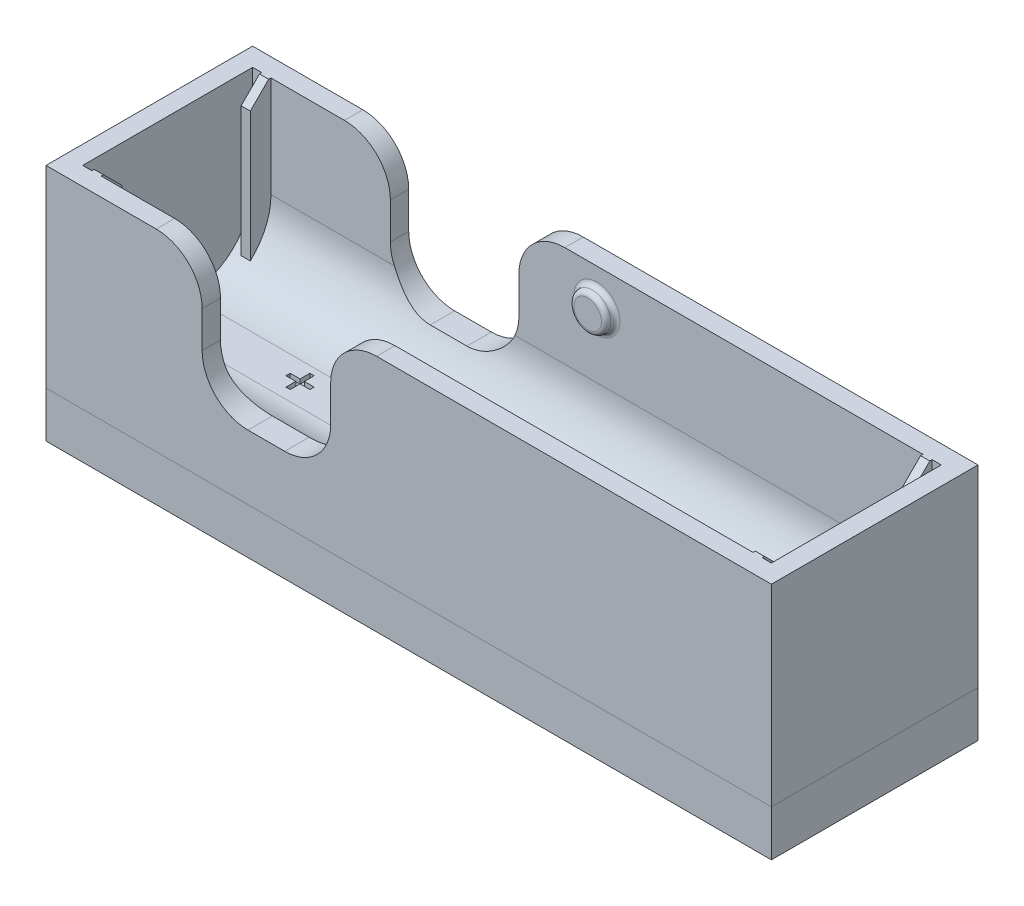
SolidWorks part; units mm, degrees
ref_plane "Спереди" through (0, 0, 0) normal (0, 0, 1) x (1, 0, 0)
ref_plane "Сверху" through (0, 0, 0) normal (0, 1, 0) x (1, 0, 0)
ref_plane "Справа" through (0, 0, 0) normal (1, 0, 0) x (0, 0, -1)
other "Configuration Table"
sketch "Эскиз1" plane through (0, 0, 0) normal (0, 1, 0) x (1, 0, 0)
  line L0 (0, 0) -> (97.2692, 0) construction
  line L1 (36.5, 9.25) -> (36.5, 7)
  line L2 (-37.5, -9.25) -> (37.5, -9.25)
  line L3 (-37.5, -9.25) -> (-37.5, 9.25)
  line L4 (-37.5, 9.25) -> (37.5, 9.25)
  line L5 (37.5, -9.25) -> (37.5, 9.25)
  line L6 (-37.5, -9.25) -> (37.5, 9.25) construction
  line L7 (-37.5, 9.25) -> (37.5, -9.25) construction
  line L8 (35.5, 9.25) -> (35.5, 7)
  line L9 (-36.5, 9.25) -> (-36.5, 7)
  line L10 (-35.5, 9.25) -> (-35.5, 7)
  line L11 (-36.5, 7) -> (-35.5, 7)
  line L12 (-36.5, -7) -> (-35.5, -7)
  line L13 (-35.5, -7) -> (-35.5, -9.25)
  line L14 (-36.5, -7) -> (-36.5, -9.25)
  line L15 (35.5, 7) -> (36.5, 7)
  line L16 (35.5, -7) -> (36.5, -7)
  line L17 (35.5, -7) -> (35.5, -9.25)
  line L18 (36.5, -7) -> (36.5, -9.25)
  line L19 (-36.5, 2.5) -> (-36.5, -2.5)
  line L20 (36.5, 2.5) -> (36.5, -2.5)
  line L21 (-37.5, 2.5) -> (-36.5, 2.5)
  line L22 (-37.5, -2.5) -> (-36.5, -2.5)
  line L23 (36.5, 2.5) -> (37.5, 2.5)
  line L24 (36.5, -2.5) -> (37.5, -2.5)
  line L25 (-39.5, 11.25) -> (39.5, 11.25)
  line L26 (39.5, -11.25) -> (39.5, 11.25)
  line L27 (-39.5, -11.25) -> (39.5, -11.25)
  line L28 (-39.5, -11.25) -> (-39.5, 11.25)
  point P1 (0, 0)
  point P34 (0, 0)
  point P39 (0, 0)
  point P40 (0, 0)
  point P41 (0, 0)
  point P42 (0, 0)
  point P43 (0, 0)
  point P44 (0, 0)
  dimension "D1" = 18.5
  dimension "D2" = 75
  dimension "D3" = 1
  dimension "D4" = 1
  dimension "D5" = 1
  dimension "D6" = 1
  dimension "D7" = 7
  dimension "D8" = 2.5
  dimension "D9" = 2.5
  dimension "D10" = 1
  dimension "D11" = 1
  dimension "D12" = 2
extrude "Бобышка-Вытянуть1" add sketch "Эскиз1" along normal blind 18 contours L28 L27 L26 L25 L5 L2 L3 L4 | L9 L11 L10 L4 | L12 L14 L2 L13 | L8 L15 L1 L4 | L18 L16 L17 L2 region at (36, 0, -8.125) region at (-36, 0, -8.125) region at (36, 0, 8.125) region at (-36, 0, 8.125) region at (0, 0, -10.4286)
extrude "Бобышка-Вытянуть2" add sketch "Эскиз1<4>" against normal blind 3 contours L28 L27 L26 L25 L5 L2 L3 L4 | L24 L20 L23 L5 L4 L1 L15 L8 L10 L11 L9 L3 L21 L19 L22 L2 L14 L12 L13 L17 L16 L18 | L12 L14 L2 L13 | L9 L11 L10 L4 | L18 L16 L17 L2 | L8 L15 L1 L4 region at (0, 0, 0) region at (36, 0, -8.125) region at (-36, 0, -8.125) region at (36, 0, 8.125) region at (-36, 0, 8.125) region at (0, 0, -10.4286)
sketch "Эскиз1<4>" plane through (0, 0, 0) normal (0, 1, 0) x (1, 0, 0) same geometry as "Эскиз1"
fillet "Скругление1" radius 7 2 edges at (0, 0, 9.25) (0, 0, -9.25)
sketch "Эскиз2" plane through (0, 0, 0) normal (0, 1, 0) x (1, 0, 0)
  text T0 "+"
  text T1 "<b>-</b>"
  point P2 (16.1974, -0.414)
  point P3 (17.3083, -1.7604)
  point P4 (19.9622, -1.093)
  point P5 (18.7279, -1.7604)
  point P6 (21.0115, -1.2781)
extrude "Вырез-Вытянуть1" cut sketch "Эскиз2" against normal blind 0.5
sketch "Эскиз3" plane through (0, 0, 11.25) normal (0, 0, 1) x (1, 0, 0)
  line L0 (-39.5, 18) -> (39.5, 18) construction
  line L1 (-21.5, 18) -> (-8.5, 18)
  line L2 (-22.4975, 13) -> (-22.4975, 9.0356)
  line L3 (-17.4975, 4.0356) -> (-13.4975, 4.0356)
  line L4 (-8.4975, 13) -> (-8.4975, 9.0356)
  line L5 (-27.5, 18) -> (-21.5, 18)
  line L6 (-8.5, 18) -> (-3.4975, 18)
  arc A0 (-13.4975, 4.0356) -> (-8.4975, 9.0356) centre (-13.4975, 9.0356) ccw
  arc A1 (-22.4975, 9.0356) -> (-17.4975, 4.0356) centre (-17.4975, 9.0356) ccw
  arc A2 (-3.4975, 18) -> (-8.4975, 13) centre (-3.4975, 13) ccw
  arc A3 (-27.5, 18) -> (-22.4975, 13) centre (-27.4975, 13) cw
  point P9 (-8.4975, 4.0356)
  point P12 (-22.4975, 4.0356)
  dimension "D4" = 5
  dimension "D5" = 5
  dimension "D1" = 14
  dimension "D2" = 14
  dimension "D3" = 18
extrude "Вырез-Вытянуть2" cut sketch "Эскиз3" against normal blind 30.5
chamfer "Фаска1" distance 2 angle 45 4 edges at (36, 18, 7) (36, 18, -7) (-36, 18, 7) (-36, 18, -7)
sketch "Эскиз4" plane through (0, 0, 9.25) normal (0, 0, -1) x (-1, 0, 0)
  line L0 (0, 0) -> (0, 28.1341) construction
  circle A0 centre (0, 14) radius 2
  point P4 (0, 14)
  dimension "D1" = 4
  dimension "D2" = 14
extrude "Бобышка-Вытянуть4" add sketch "Эскиз4" along normal blind 1
sketch "Эскиз5" plane through (0, 0, -9.25) normal (0, 0, 1) x (1, 0, 0)
  line L0 (0, 0) -> (0, 24.5494) construction
  circle A0 centre (0, 14) radius 2
  dimension "D1" = 4
  dimension "D2" = 14
extrude "Бобышка-Вытянуть5" add sketch "Эскиз5" along normal blind 1
fillet "Скругление3" radius 0.5 4 edges at (-2, 14, 8.25) (-2, 14, 9.25) (2, 14, -8.25) (-2, 14, -9.25)
sketch "Эскиз6" plane through (0, -3, 0) normal (0, -1, 0) x (1, 0, 0)
  line L0 (-37.5, 6.25) -> (-37.5, -6.25)
  line L1 (-39.5, 11.25) -> (39.5, 11.25)
  line L2 (-39.5, 11.25) -> (-39.5, -11.25)
  line L3 (-39.5, -11.25) -> (39.5, -11.25)
  line L4 (39.5, 11.25) -> (39.5, -11.25)
  line L5 (-34.5, -9.25) -> (34.5, -9.25)
  line L6 (37.5, 6.25) -> (37.5, -6.25)
  line L7 (-34.5, 9.25) -> (34.5, 9.25)
  line L8 (-39.5, 6.25) -> (-34.5, 11.25) construction
  line L9 (-39.5, 11.25) -> (-34.5, 11.25)
  line L10 (-39.5, 11.25) -> (-39.5, 6.25)
  line L11 (-39.5, 6.25) -> (-36.5, 6.25)
  line L12 (-34.5, 11.25) -> (-34.5, 8.25)
  line L13 (-39.5, -11.25) -> (-34.5, -11.25)
  line L14 (-39.5, -11.25) -> (-39.5, -6.25)
  line L15 (-39.5, -6.25) -> (-36.5, -6.25)
  line L16 (-34.5, -11.25) -> (-34.5, -8.25)
  line L17 (39.5, -11.25) -> (34.5, -11.25)
  line L18 (39.5, -11.25) -> (39.5, -6.25)
  line L19 (39.5, -6.25) -> (36.5, -6.25)
  line L20 (34.5, -11.25) -> (34.5, -8.25)
  line L21 (39.5, 11.25) -> (34.5, 11.25)
  line L22 (39.5, 11.25) -> (39.5, 6.25)
  line L23 (39.5, 6.25) -> (36.5, 6.25)
  line L24 (34.5, 11.25) -> (34.5, 8.25)
  line L25 (-37.5, 9.25) -> (37.5, 9.25) construction
  line L26 (-37.5, 9.25) -> (-37.5, -9.25) construction
  line L27 (-37.5, -9.25) -> (37.5, -9.25) construction
  line L28 (37.5, 9.25) -> (37.5, -9.25) construction
  line L29 (-39.5, -6.25) -> (-34.5, -11.25) construction
  line L30 (34.5, 11.25) -> (39.5, 6.25) construction
  line L31 (34.5, -11.25) -> (39.5, -6.25) construction
  arc A0 (36.5, -6.25) -> (34.5, -8.25) centre (36.5, -8.25) ccw
  arc A1 (34.5, 8.25) -> (36.5, 6.25) centre (36.5, 8.25) ccw
  arc A2 (-34.5, -8.25) -> (-36.5, -6.25) centre (-36.5, -8.25) ccw
  arc A3 (-34.5, 8.25) -> (-36.5, 6.25) centre (-36.5, 8.25) cw
  circle A4 centre (-37, 8.75) radius 0.5
  circle A5 centre (37, 8.75) radius 0.5
  circle A6 centre (37, -8.75) radius 0.5
  circle A7 centre (-37, -8.75) radius 0.5
  point P38 (-34.5, 6.25)
  point P39 (-37, 8.75)
  point P40 (-37, -8.75)
  point P41 (37, -8.75)
  point P42 (37, 8.75)
  line M9 (37.5, 2.5) -> (37.5, -2.5)
  line M16 (-37.5, -2.5) -> (-37.5, 2.5)
  line M17 (-39.5, 11.25) -> (-39.5, -11.25)
  line M18 (-39.5, -11.25) -> (39.5, -11.25)
  line M19 (39.5, -11.25) -> (39.5, 11.25)
  line M20 (39.5, 11.25) -> (-39.5, 11.25)
  dimension "D3" = 2
  dimension "D4" = 1
  dimension "D2" = 5
  dimension "D1" = 2
extrude "Бобышка-Вытянуть6" add sketch "Эскиз6" along normal blind 5 separate body contours A3 L12 L1 L11 A4 M17 | L24 L1 L12 L7 | L2 L15 L0 L11 M16 | L16 A2 L15 A7 M17 M18 | L3 L20 L5 L16 | L24 A1 L23 A5 M19 M20 | L4 L23 L6 L19 M9 | L19 A0 L20 A6 M18 M19 region at (-38.5, -3, 0) region at (-38.5, -3, 6.3207) region at (-38.5, -3, -6.3207) region at (0, -3, 10.25) region at (37, -3, 11.1793) region at (0, -3, -10.25) region at (34.5707, -3, -10.25) region at (38.5, -3, 0)
extrude "Вырез-Вытянуть3" cut sketch "Эскиз6<3>" against normal blind 3 contours A7 | A4 | A6 | A5 region at (-37, -3, 8.75) region at (37, -3, 8.75) region at (37, -3, -8.75) region at (-37, -3, -8.75)
sketch "Эскиз6<3>" plane through (0, -3, 0) normal (0, -1, 0) x (1, 0, 0) same geometry as "Эскиз6"
